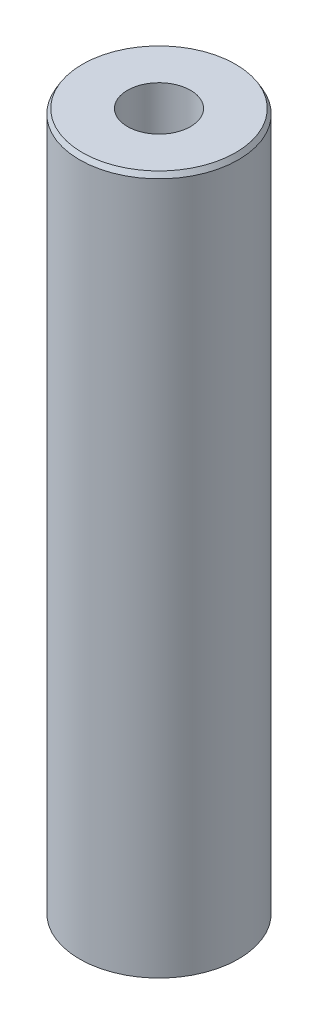
SolidWorks part; units mm, degrees
ref_plane "Front Plane" through (0, 0, 0) normal (0, 0, 1) x (1, 0, 0)
ref_plane "Top Plane" through (0, 0, 0) normal (0, 1, 0) x (1, 0, 0)
ref_plane "Right Plane" through (0, 0, 0) normal (1, 0, 0) x (0, 0, -1)
sketch "Sketch1" plane through (0, 0, 0) normal (0, 1, 0) x (1, 0, 0)
  circle A0 centre (0, 0) radius 47.5
  dimension "SHAFT_OD" = 95
extrude "Boss-Extrude1" add sketch "Sketch1" along normal blind 418.6976
sketch "Sketch2" plane through (0, 0, 0) normal (0, 1, 0) x (1, 0, 0)
  circle A0 centre (0, 0) radius 18.862
  dimension "BORE_D" = 37.7239
extrude "Cut-Extrude1" cut sketch "Sketch2" along normal through all
chamfer "Chamfer1" distance 2.8879 angle 30 2 edges at (0, 418.6976, 47.5) (0, 0, 47.5) first distance on face at (0, 418.6976, 47.5) first distance on face at (0, 0, 18.862)
